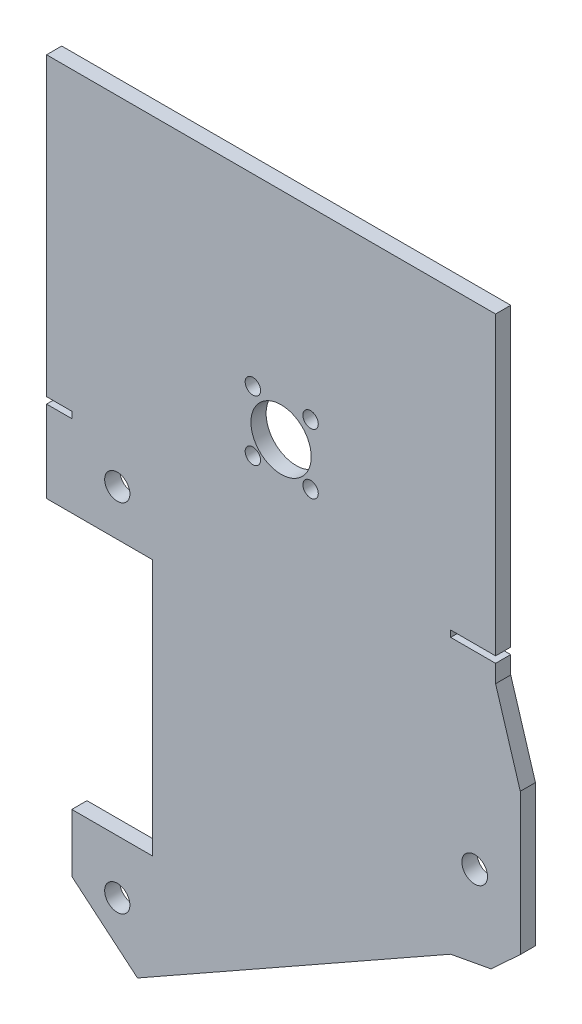
SolidWorks part; units mm, degrees
ref_plane "Front Plane" through (0, 0, 0) normal (0, 0, 1) x (1, 0, 0)
ref_plane "Top Plane" through (0, 0, 0) normal (0, 1, 0) x (1, 0, 0)
ref_plane "Right Plane" through (0, 0, 0) normal (1, 0, 0) x (0, 0, -1)
sketch "Sketch1" plane through (0, 0, 0) normal (0, 0, 1) x (1, 0, 0)
  line L0 (0, 0) -> (88.9, 0)
  line L1 (88.9, 0) -> (88.9, -3.5)
  line L2 (88.9, -3.5) -> (93.7917, -19.5)
  line L3 (93.7917, -19.5) -> (93.7917, -47.5)
  line L4 (0, 0) -> (0, -16.2)
  line L5 (0, -16.2) -> (21, -16.2)
  line L6 (21, -16.2) -> (21, -67)
  line L7 (21, -67) -> (5, -67)
  line L8 (5, -67) -> (5, -78.5)
  line L9 (5, -78.5) -> (18, -89.4083)
  line L10 (18, -89.4083) -> (80, -54.3304)
  line L11 (80, -54.3304) -> (88, -52.8477)
  line L12 (88, -52.8477) -> (93.7917, -47.5)
  dimension "D1" = 88.9
  dimension "D2" = 3.5
  dimension "D3" = 163
  dimension "D4" = 16
  dimension "D5" = 28
  dimension "D6" = 89.4083
  dimension "D7" = 21
  dimension "D8" = 50.8
  dimension "D9" = 16
  dimension "D10" = 11.5
  dimension "D11" = 130
  dimension "D12" = 13
  dimension "D13" = 110.5
  dimension "D14" = 62
  dimension "D15" = 8
  dimension "D16" = 161
extrude "Boss-Extrude1" add sketch "Sketch1" along normal blind 3
sketch "Sketch2" plane through (0, 0, 0) normal (0, 1, 0) x (1, 0, 0)
  line L0 (45.8978, 14) -> (40.3978, 14) construction
  line L1 (0, -3) -> (88.9, -3)
  line L2 (0, -3) -> (0, 54)
  line L3 (0, 54) -> (88.9, 54)
  line L4 (88.9, -3) -> (88.9, 54)
  circle A0 centre (40.3978, 8.5) radius 1.5
  circle A1 centre (40.3978, 20) radius 1.5
  circle A2 centre (51.8978, 8.5) radius 1.5
  circle A3 centre (51.8978, 20) radius 1.5
  ellipse E0 centre (45.8978, 14) end of major axis (45.8978, 8) minor radius 5.5
  dimension "D9" = 3
  dimension "D10" = 3
  dimension "D11" = 3
  dimension "D12" = 3
  dimension "D1" = 88.9
  dimension "D2" = 57
  dimension "D3" = 45.8978
  dimension "D4" = 5.5
  dimension "D5" = 11.5
  dimension "D6" = 23
  dimension "D7" = 11.5
  dimension "D8" = 17
  dimension "D13" = 12
  dimension "D14" = 11
extrude "Boss-Extrude2" add sketch "Sketch2" along normal blind 3
ref_plane "Plane1" through (85.9, 0, 0) normal (1, 0, 0) x (0, 0, -1)
sketch "Sketch3" plane through (85.9, 0, 0) normal (1, 0, 0) x (0, 0, -1)
  line L0 (11.5, 0) -> (0, 0)
  line L1 (0, 0) -> (54, 0) construction
  line L2 (0, 0) -> (0, -11.5)
  line L3 (0, -19.5) -> (0, -3.5) construction
  line L4 (0, -11.5) -> (11.5, 0)
  dimension "D1" = 11.5
  dimension "D2" = 11.5
extrude "Boss-Extrude3" add sketch "Sketch3" against normal blind 84.5
sketch "Sketch4" plane through (0, 0, 0) normal (0, 0, -1) x (-1, 0, 0)
  line L0 (-1.4, -11.5) -> (-85.9, -11.5) construction
  line L1 (-81.4, -11.5) -> (-6.4, -11.5)
  line L2 (-81.4, -11.5) -> (-81.4, 0)
  line L3 (-81.4, 0) -> (-6.4, 0)
  line L4 (-6.4, -11.5) -> (-6.4, 0)
  line L5 (-50.8976, 0) -> (-85.9, 0) construction
  line L6 (-85.9, 13.7659) -> (-85.9, -13.7659) construction
  dimension "D1" = 75
  dimension "D2" = 4.5
extrude "Cut-Extrude2" cut sketch "Sketch4" along normal blind 84.5
sketch "Sketch6" plane through (0, 0, 3) normal (0, 0, 1) x (1, 0, 0)
  line L0 (0, 3) -> (0, -16.2) construction
  line L1 (0, 3) -> (88.9, 3) construction
  circle A0 centre (14, -77.66) radius 2.5
  circle A1 centre (84.763, -37.386) radius 2.54
  circle A2 centre (14, -7.16) radius 2.5
  dimension "D1" = 5
  dimension "D2" = 5
  dimension "D3" = 5.08
  dimension "D4" = 14
  dimension "D5" = 10.16
  dimension "D6" = 70.5
  dimension "D7" = 14
  dimension "D8" = 40.386
  dimension "D9" = 70.763
extrude "Cut-Extrude3" cut sketch "Sketch6" against normal blind 84.5
sketch "Sketch7" plane through (0, 0, 0) normal (0, -1, 0) x (1, 0, 0)
  line L1 (88.9, -54) -> (0, -54)
  line L2 (88.9, -54) -> (88.9, 0)
  line L3 (88.9, 0) -> (0, 0)
  line L4 (0, -54) -> (0, 0)
extrude "Cut-Extrude4" cut sketch "Sketch7" against normal through all both and the other way through all
sketch "Sketch8" plane through (0, 0, 0) normal (0, 0, -1) x (-1, 0, 0)
  line L0 (-88.9, 3) -> (0, 3) construction
  line L1 (-88.9, 3) -> (0, 3)
  line L2 (-88.9, 3) -> (-88.9, 59.896)
  line L3 (-88.9, 59.896) -> (0, 59.896)
  line L4 (0, 3) -> (0, 59.896)
  line L5 (-46.4315, 17.1375) -> (-40.4625, 17.1375) construction
  line L6 (-14, -77.66) -> (-84.763, -77.66) construction
  line L7 (-84.763, -77.66) -> (-84.763, -37.386) construction
  line L8 (-49.3815, -77.66) -> (-49.3815, 51.3441) construction
  line L9 (-58.3815, 3) -> (-58.3815, 17.1375) construction
  line L10 (-58.3815, 17.1375) -> (-46.4315, 17.1375) construction
  circle A0 centre (-46.4315, 17.1375) radius 5.969
  circle A1 centre (-40.8435, 23.4875) radius 1.524
  circle A2 centre (-40.8435, 11.5495) radius 1.524
  circle A3 centre (-52.2735, 23.4875) radius 1.524
  circle A4 centre (-52.2735, 11.5495) radius 1.524
  dimension "D8" = 11.938
  dimension "D9" = 3.048
  dimension "D10" = 3.048
  dimension "D11" = 3.048
  dimension "D12" = 3.048
  dimension "D1" = 56.896
  dimension "D2" = 88.9
  dimension "D3" = 14.1375
  dimension "D4" = 5.588
  dimension "D5" = 2.95
  dimension "D6" = 11.938
  dimension "D7" = 5.588
  dimension "D14" = 11.43
extrude "Boss-Extrude4" add sketch "Sketch8" against normal up to surface (3 mm away) up to face at (16.5, -77.66, 3)
sketch "Sketch10" plane through (0, 0, 0) normal (0, 0, -1) x (-1, 0, 0)
  line L0 (-88.9, -3.5) -> (-88.9, 59.896) construction
  line L1 (0, 0) -> (-5.08, 0)
  line L2 (0, 0) -> (0, 1.27)
  line L3 (0, 1.27) -> (-5.08, 1.27)
  line L4 (-5.08, 0) -> (-5.08, 1.27)
  line L5 (-80.01, 0) -> (-88.9, 0)
  line L6 (-80.01, 0) -> (-80.01, 1.27)
  line L7 (-80.01, 1.27) -> (-88.9, 1.27)
  line L8 (-88.9, 0) -> (-88.9, 1.27)
  dimension "D1" = 5.08
  dimension "D2" = 1.27
  dimension "D3" = 8.89
  dimension "D4" = 1.27
extrude "Cut-Extrude5" cut sketch "Sketch10" against normal blind 10
